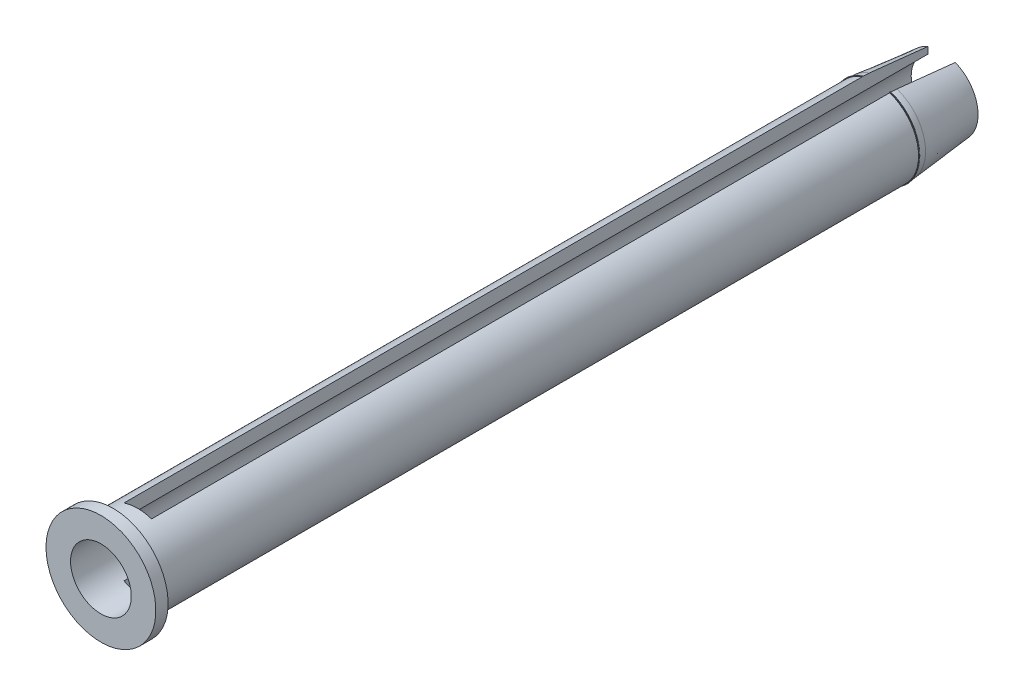
SolidWorks part; units mm, degrees
ref_plane "Alzado" through (0, 0, 0) normal (1, 0, 0) x (0, 1, 0)
ref_plane "Planta" through (0, 0, 0) normal (0, 0, 1) x (0, 1, 0)
ref_plane "Vista lateral" through (0, 0, 0) normal (0, 1, 0) x (-1, 0, 0)
sketch "Croquis1" plane through (0, 0, 0) normal (1, 0, 0) x (0, 1, 0)
  line L0 (4.95, -68.5) -> (4.95, 68.5)
  line L1 (4.95, 68.5) -> (8.95, 68.5)
  line L2 (8.95, 68.5) -> (8.95, 66.5)
  line L3 (8.95, 66.5) -> (6.95, 66.5)
  line L4 (6.95, 66.5) -> (6.95, -68.5)
  line L8 (0, 0) -> (0, 4.1277) construction
  line L9 (6.95, -68.5) -> (4.95, -68.5)
  point P3 (4.95, 0)
  dimension "D1" = 2
  dimension "D4" = 2
  dimension "D5" = 2
  dimension "D2" = 135
  dimension "D3" = 13.9
revolve "Revolución1" add sketch "Croquis1" angle 360 about L8
chamfer "Chaflán2" distance 10 distance2 1 1 edges at (-6.95, 0, -68.5) first distance on face at (-6.95, 0, 66.5)
fillet "Redondeo1" radius 10 1 edges at (-6.95, 0, -58.5)
sketch "Croquis3" plane through (0, 0, -68.5) normal (0, 0, -1) x (1, 0, 0)
  circle A1 centre (0, 0) radius 6.95 construction
  circle A2 centre (0, 0) radius 7.05
  circle A4 centre (0, 0) radius 6.95
  dimension "D1" = 0.1
extrude "Saliente-Extruir1" add sketch "Croquis3" against normal blind 0.2 from offset 10.5 contours A2 region at (-7.0301, 0, -68.5) offset against normal yes
sketch "Croquis2" plane through (0, 0, -68.5) normal (0, 0, -1) x (1, 0, 0)
  line L1 (-2.25, -8.6626) -> (2.25, -8.6626)
  line L2 (-2.25, -8.6626) -> (-2.25, 8.6626)
  line L3 (-2.25, 8.6626) -> (2.25, 8.6626)
  line L4 (2.25, -8.6626) -> (2.25, 8.6626)
  line L5 (-2.25, -8.6626) -> (2.25, 8.6626) construction
  line L6 (-2.25, 8.6626) -> (2.25, -8.6626) construction
  circle A0 centre (0, 0) radius 8.95 construction
  point P0 (0, 0)
  dimension "D1" = 4.5
extrude "Cortar-Extruir1" cut sketch "Croquis2" against normal offset from surface (131 mm away) 4 up to face at (-8.95, 0, 66.5)
chamfer "Chaflán3" distance 0.1 distance2 0.1 2 edges at (7.05, 0, -58) (-7.05, 0, -58)
fillet "Redondeo2" radius 0.05 4 edges at (7.05, 0, -57.8) (7.05, 0, -57.9) (-7.05, 0, -57.9) (-7.05, 0, -57.8)
equation "\"D5@Croquis1\"=\"D4@Croquis1\""
